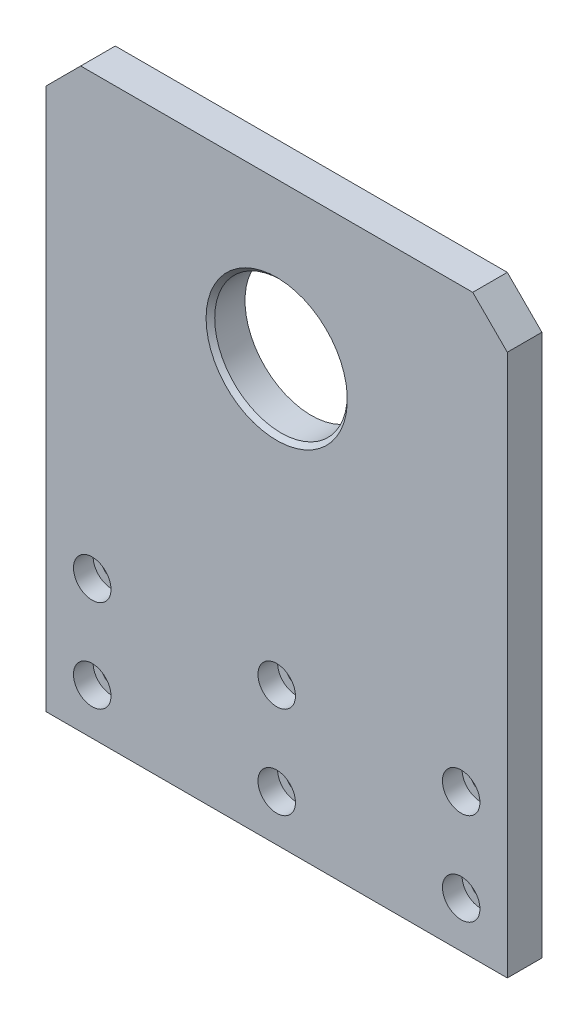
SolidWorks part; units mm, degrees
material "6061-T6 (SS)"
ref_plane "Front Plane" through (0, 0, 0) normal (0, 0, 1) x (1, 0, 0)
ref_plane "Top Plane" through (0, 0, 0) normal (0, 1, 0) x (1, 0, 0)
ref_plane "Right Plane" through (0, 0, 0) normal (1, 0, 0) x (0, 0, -1)
sketch "Sketch1" plane through (0, 0, 0) normal (0, 0, 1) x (1, 0, 0)
  line L1 (0, 0) -> (80, 0)
  line L2 (0, 0) -> (0, 100)
  line L3 (0, 100) -> (80, 100)
  line L4 (80, 0) -> (80, 100)
  dimension "D1" = 100
  dimension "D2" = 80
extrude "Boss-Extrude1" add sketch "Sketch1" along normal blind 6
sketch "Sketch2" plane through (0, 0, 6) normal (0, 0, 1) x (1, 0, 0)
  line L0 (0, 100) -> (0, 0) construction
  line L1 (0, 0) -> (80, 0) construction
  line L2 (80, 0) -> (80, 100) construction
  point P0 (8, 8)
  point P6 (40, 8)
  point P7 (72, 8)
  point P8 (40, 24)
  point P9 (72, 24)
  point P10 (8, 24)
  dimension "D3" = 8
  dimension "D4" = 8
  dimension "D5" = 8
  dimension "D6" = 16
  dimension "D2" = 3
  dimension "D1" = 2
hole_wizard "CBORE for M3 Hex Socket Head Cap Screw1" positions "Sketch2" profile "Sketch3" counterbore size "M3" standard "DIN" end condition through all
sketch "Sketch3" plane through (8, 8, 6) normal (1, 0, 0) x (0, -1, 0)
  line L0 (0, 0) -> (0, 6)
  line L1 (0, 6) -> (1.7, 6)
  line L3 (1.7, 6) -> (1.7, 3.4)
  line L4 (1.7, 3.4) -> (3.25, 3.4)
  line L5 (3.25, 3.4) -> (3.25, 0)
  line L7 (3.25, 0) -> (0, 0)
  line L11 (0, -6.35) -> (0, 107.95) construction
  dimension "Thru Hole Dia." = 3.4
  dimension "Thru Hole Depth" = 6
  dimension "C'Bore Dia." = 6.5
  dimension "C'Bore Depth" = 3.4
sketch "Sketch4" plane through (0, 0, 6) normal (0, 0, 1) x (1, 0, 0)
  line L0 (0, 0) -> (80, 0) construction
  line L1 (40, 73) -> (40, 0) construction
  circle A0 centre (40, 73) radius 11.5
  dimension "D1" = 23
  dimension "D2" = 73
extrude "Cut-Extrude1" cut sketch "Sketch4" against normal through all
chamfer "Chamfer1" distance 0.75 angle 45 1 edges at (51.5, 73, 6)
chamfer "Chamfer2" distance 6 angle 45 2 edges at (0, 100, 3) (80, 100, 3)
